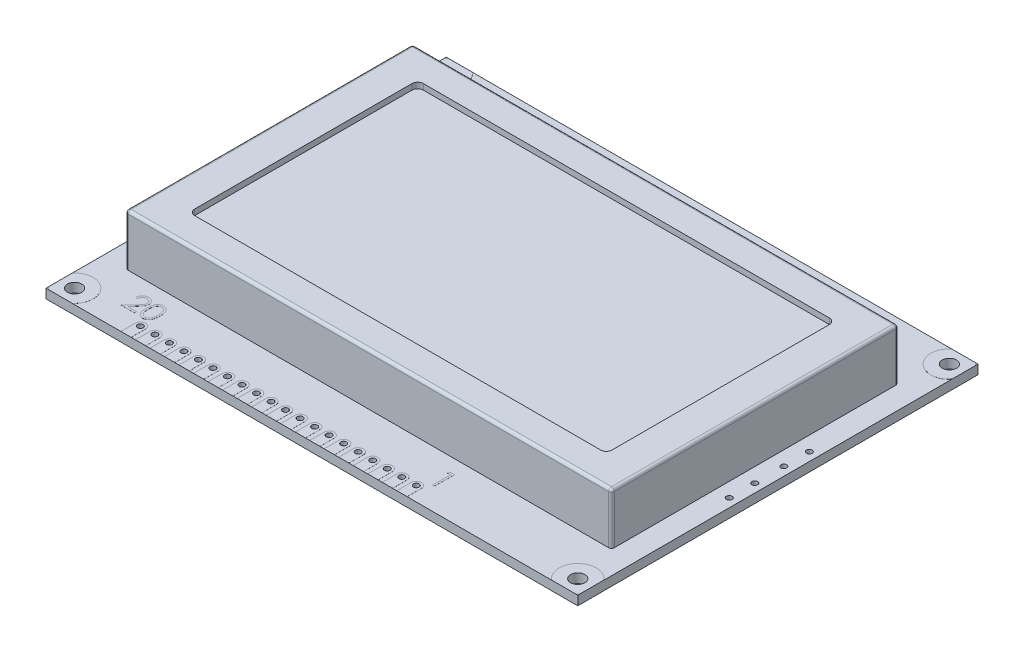
SolidWorks part; units mm, degrees
material "A-Glass Fiber"
ref_plane "Front Plane" through (0, 0, 0) normal (0, 0, 1) x (1, 0, 0)
ref_plane "Top Plane" through (0, 0, 0) normal (0, 1, 0) x (1, 0, 0)
ref_plane "Right Plane" through (0, 0, 0) normal (1, 0, 0) x (0, 0, -1)
sketch "Sketch1" plane through (0, 0, 0) normal (0, 1, 0) x (1, 0, 0)
  line L0 (2.5, 67.5) -> (90.5, 67.5) construction
  line L1 (0, 0) -> (93, 0)
  line L2 (0, 0) -> (0, 70)
  line L3 (0, 70) -> (93, 70)
  line L4 (93, 0) -> (93, 70)
  line L5 (2.5, 2.5) -> (90.5, 2.5) construction
  line L6 (90.5, 2.5) -> (90.5, 67.5) construction
  line L7 (2.5, 67.5) -> (2.5, 2.5) construction
  line L8 (90.5, 35) -> (91.5, 35) construction
  line L9 (91.5, 37.54) -> (91.5, 32.46) construction
  line L10 (91.5, 37.54) -> (91.5, 42) construction
  line L11 (91.5, 32.46) -> (91.5, 28) construction
  circle A0 centre (2.5, 67.5) radius 1.25
  circle A1 centre (90.5, 67.5) radius 1.25
  circle A2 centre (90.5, 2.5) radius 1.25
  circle A3 centre (2.5, 2.5) radius 1.25
  circle A4 centre (14, 2.5) radius 0.5
  circle A5 centre (16.54, 2.5) radius 0.5
  circle A6 centre (19.08, 2.5) radius 0.5
  circle A7 centre (21.62, 2.5) radius 0.5
  circle A8 centre (24.16, 2.5) radius 0.5
  circle A9 centre (26.7, 2.5) radius 0.5
  circle A10 centre (29.24, 2.5) radius 0.5
  circle A11 centre (31.78, 2.5) radius 0.5
  circle A12 centre (34.32, 2.5) radius 0.5
  circle A13 centre (36.86, 2.5) radius 0.5
  circle A14 centre (39.4, 2.5) radius 0.5
  circle A15 centre (41.94, 2.5) radius 0.5
  circle A16 centre (44.48, 2.5) radius 0.5
  circle A17 centre (47.02, 2.5) radius 0.5
  circle A18 centre (49.56, 2.5) radius 0.5
  circle A19 centre (52.1, 2.5) radius 0.5
  circle A20 centre (54.64, 2.5) radius 0.5
  circle A21 centre (57.18, 2.5) radius 0.5
  circle A22 centre (59.72, 2.5) radius 0.5
  circle A23 centre (62.26, 2.5) radius 0.5
  circle A24 centre (91.5, 42) radius 0.5
  circle A25 centre (91.5, 37.54) radius 0.5
  circle A26 centre (91.5, 32.46) radius 0.5
  circle A27 centre (91.5, 28) radius 0.5
  point P57 (91.5, 35)
  dimension "D3" = 2.5
  dimension "D9" = 1
  dimension "D13" = 1
  dimension "D1" = 93
  dimension "D2" = 70
  dimension "D4" = 2.5
  dimension "D5" = 2.5
  dimension "D6" = 2.5
  dimension "D7" = 2.5
  dimension "D8" = 14
  dimension "D11" = 5.08
  dimension "D12" = 14
  dimension "D14" = 1.5
  dimension "D10" = 20
extrude "Boss-Extrude1" add sketch "Sketch1" along normal blind 1.6
sketch "Sketch4" plane through (0, 0, 0) normal (0, 1, 0) x (1, 0, 0)
  line L0 (13.1, 2.5) -> (13.1, 0)
  line L1 (0, 0) -> (93, 0) construction
  line L2 (13.1, 0) -> (14.9, 0)
  line L3 (14.9, 0) -> (14.9, 2.5)
  line L4 (15.64, 2.5) -> (15.64, 0)
  line L5 (15.64, 0) -> (17.44, 0)
  line L6 (17.44, 0) -> (17.44, 2.5)
  line L7 (18.18, 2.5) -> (18.18, 0)
  line L8 (18.18, 0) -> (19.98, 0)
  line L9 (19.98, 0) -> (19.98, 2.5)
  line L10 (20.72, 2.5) -> (20.72, 0)
  line L11 (20.72, 0) -> (22.52, 0)
  line L12 (22.52, 0) -> (22.52, 2.5)
  line L13 (23.26, 2.5) -> (23.26, 0)
  line L14 (23.26, 0) -> (25.06, 0)
  line L15 (25.06, 0) -> (25.06, 2.5)
  line L16 (25.8, 2.5) -> (25.8, 0)
  line L17 (25.8, 0) -> (27.6, 0)
  line L18 (27.6, 0) -> (27.6, 2.5)
  line L19 (28.34, 2.5) -> (28.34, 0)
  line L20 (28.34, 0) -> (30.14, 0)
  line L21 (30.14, 0) -> (30.14, 2.5)
  line L22 (30.88, 2.5) -> (30.88, 0)
  line L23 (30.88, 0) -> (32.68, 0)
  line L24 (32.68, 0) -> (32.68, 2.5)
  line L25 (33.42, 2.5) -> (33.42, 0)
  line L26 (33.42, 0) -> (35.22, 0)
  line L27 (35.22, 0) -> (35.22, 2.5)
  line L28 (35.96, 2.5) -> (35.96, 0)
  line L29 (35.96, 0) -> (37.76, 0)
  line L30 (37.76, 0) -> (37.76, 2.5)
  line L31 (38.5, 2.5) -> (38.5, 0)
  line L32 (38.5, 0) -> (40.3, 0)
  line L33 (40.3, 0) -> (40.3, 2.5)
  line L34 (41.04, 2.5) -> (41.04, 0)
  line L35 (41.04, 0) -> (42.84, 0)
  line L36 (42.84, 0) -> (42.84, 2.5)
  line L37 (43.58, 2.5) -> (43.58, 0)
  line L38 (43.58, 0) -> (45.38, 0)
  line L39 (45.38, 0) -> (45.38, 2.5)
  line L40 (46.12, 2.5) -> (46.12, 0)
  line L41 (46.12, 0) -> (47.92, 0)
  line L42 (47.92, 0) -> (47.92, 2.5)
  line L43 (48.66, 2.5) -> (48.66, 0)
  line L44 (48.66, 0) -> (50.46, 0)
  line L45 (50.46, 0) -> (50.46, 2.5)
  line L46 (51.2, 2.5) -> (51.2, 0)
  line L47 (51.2, 0) -> (53, 0)
  line L48 (53, 0) -> (53, 2.5)
  line L49 (53.74, 2.5) -> (53.74, 0)
  line L50 (53.74, 0) -> (55.54, 0)
  line L51 (55.54, 0) -> (55.54, 2.5)
  line L52 (56.28, 2.5) -> (56.28, 0)
  line L53 (56.28, 0) -> (58.08, 0)
  line L54 (58.08, 0) -> (58.08, 2.5)
  line L55 (58.82, 2.5) -> (58.82, 0)
  line L56 (58.82, 0) -> (60.62, 0)
  line L57 (60.62, 0) -> (60.62, 2.5)
  line L58 (61.36, 2.5) -> (61.36, 0)
  line L59 (61.36, 0) -> (63.16, 0)
  line L60 (63.16, 0) -> (63.16, 2.5)
  line L61 (0, 4.5767) -> (0, 0.4233)
  line L62 (0, 70) -> (0, 0) construction
  line L63 (0.4233, 0) -> (4.5767, 0)
  line L64 (4.5767, 70) -> (0.4233, 70)
  line L65 (93, 70) -> (0, 70) construction
  line L66 (0, 69.5767) -> (0, 65.4233)
  line L67 (88.4233, 70) -> (92.5767, 70)
  line L68 (93, 69.5767) -> (93, 65.4233)
  line L69 (93, 0) -> (93, 70) construction
  line L70 (88.4233, 0) -> (92.5767, 0)
  line L71 (93, 4.5767) -> (93, 0.4233)
  arc A0 (13.1, 2.5) -> (14.9, 2.5) centre (14, 2.5) cw
  circle A1 centre (14, 2.5) radius 0.5
  arc A2 (15.64, 2.5) -> (17.44, 2.5) centre (16.54, 2.5) cw
  circle A3 centre (16.54, 2.5) radius 0.5
  arc A4 (18.18, 2.5) -> (19.98, 2.5) centre (19.08, 2.5) cw
  circle A5 centre (19.08, 2.5) radius 0.5
  arc A6 (20.72, 2.5) -> (22.52, 2.5) centre (21.62, 2.5) cw
  circle A7 centre (21.62, 2.5) radius 0.5
  arc A8 (23.26, 2.5) -> (25.06, 2.5) centre (24.16, 2.5) cw
  circle A9 centre (24.16, 2.5) radius 0.5
  arc A10 (25.8, 2.5) -> (27.6, 2.5) centre (26.7, 2.5) cw
  circle A11 centre (26.7, 2.5) radius 0.5
  arc A12 (28.34, 2.5) -> (30.14, 2.5) centre (29.24, 2.5) cw
  circle A13 centre (29.24, 2.5) radius 0.5
  arc A14 (30.88, 2.5) -> (32.68, 2.5) centre (31.78, 2.5) cw
  circle A15 centre (31.78, 2.5) radius 0.5
  arc A16 (33.42, 2.5) -> (35.22, 2.5) centre (34.32, 2.5) cw
  circle A17 centre (34.32, 2.5) radius 0.5
  arc A18 (35.96, 2.5) -> (37.76, 2.5) centre (36.86, 2.5) cw
  circle A19 centre (36.86, 2.5) radius 0.5
  arc A20 (38.5, 2.5) -> (40.3, 2.5) centre (39.4, 2.5) cw
  circle A21 centre (39.4, 2.5) radius 0.5
  arc A22 (41.04, 2.5) -> (42.84, 2.5) centre (41.94, 2.5) cw
  circle A23 centre (41.94, 2.5) radius 0.5
  arc A24 (43.58, 2.5) -> (45.38, 2.5) centre (44.48, 2.5) cw
  circle A25 centre (44.48, 2.5) radius 0.5
  arc A26 (46.12, 2.5) -> (47.92, 2.5) centre (47.02, 2.5) cw
  circle A27 centre (47.02, 2.5) radius 0.5
  arc A28 (48.66, 2.5) -> (50.46, 2.5) centre (49.56, 2.5) cw
  circle A29 centre (49.56, 2.5) radius 0.5
  arc A30 (51.2, 2.5) -> (53, 2.5) centre (52.1, 2.5) cw
  circle A31 centre (52.1, 2.5) radius 0.5
  arc A32 (53.74, 2.5) -> (55.54, 2.5) centre (54.64, 2.5) cw
  circle A33 centre (54.64, 2.5) radius 0.5
  arc A34 (56.28, 2.5) -> (58.08, 2.5) centre (57.18, 2.5) cw
  circle A35 centre (57.18, 2.5) radius 0.5
  arc A36 (58.82, 2.5) -> (60.62, 2.5) centre (59.72, 2.5) cw
  circle A37 centre (59.72, 2.5) radius 0.5
  arc A38 (61.36, 2.5) -> (63.16, 2.5) centre (62.26, 2.5) cw
  circle A39 centre (62.26, 2.5) radius 0.5
  arc A40 (0, 0.4233) -> (0.4233, 0) centre (2.5, 2.5) ccw
  circle A41 centre (2.5, 2.5) radius 1.25
  circle A42 centre (90.5, 67.5) radius 1.25
  arc A43 (88.4233, 70) -> (93, 65.4233) centre (90.5, 67.5) ccw
  circle A44 centre (2.5, 67.5) radius 1.25
  arc A45 (0.4233, 70) -> (0, 69.5767) centre (2.5, 67.5) ccw
  circle A46 centre (90.5, 2.5) radius 1.25
  arc A47 (93, 4.5767) -> (88.4233, 0) centre (90.5, 2.5) ccw
  arc A48 (4.5767, 0) -> (0, 4.5767) centre (2.5, 2.5) ccw
  arc A49 (0, 65.4233) -> (4.5767, 70) centre (2.5, 67.5) ccw
  arc A50 (93, 69.5767) -> (92.5767, 70) centre (90.5, 67.5) ccw
  arc A51 (92.5767, 0) -> (93, 0.4233) centre (90.5, 2.5) ccw
  dimension "D1" = 20
  dimension "D2" = 0.9
  dimension "D3" = 6.5
extrude "Boss-Extrude2" add sketch "Sketch4" along normal blind 1.61 and the other way blind 0.01
sketch "Sketch5" plane through (0, 0, 0) normal (0, 1, 0) x (1, 0, 0)
  line L0 (0, 70) -> (93, 0) construction
  line L2 (4, 60.1) -> (89, 60.1)
  line L3 (4, 60.1) -> (4, 9.9)
  line L4 (4, 9.9) -> (89, 9.9)
  line L5 (89, 60.1) -> (89, 9.9)
  line L6 (4, 60.1) -> (89, 9.9) construction
  line L7 (4, 9.9) -> (89, 60.1) construction
  point P4 (46.5, 35)
  dimension "D1" = 50.2
  dimension "D2" = 85
extrude "Boss-Extrude3" add sketch "Sketch5" along normal blind 9 from surface starting at face at (91.5, 1.6, -27.5)
fillet "Fillet1" radius 0.5 8 edges at (89, 6.1, -9.9) (89, 6.1, -60.1) (89, 10.6, -35) (46.5, 10.6, -60.1) (4, 6.1, -60.1) (46.5, 10.6, -9.9) (4, 10.6, -35) (4, 6.1, -9.9)
sketch "Sketch6" plane through (0, 0, 0) normal (0, 1, 0) x (1, 0, 0)
  line L0 (0, 70) -> (93, 0) construction
  line L2 (11, 55) -> (82, 55)
  line L3 (10, 54) -> (10, 16)
  line L4 (11, 15) -> (82, 15)
  line L5 (83, 54) -> (83, 16)
  line L6 (10, 55) -> (83, 15) construction
  line L7 (10, 15) -> (83, 55) construction
  arc A0 (82, 55) -> (83, 54) centre (82, 54) cw
  arc A1 (82, 15) -> (83, 16) centre (82, 16) ccw
  arc A2 (10, 16) -> (11, 15) centre (11, 16) ccw
  arc A3 (11, 55) -> (10, 54) centre (11, 54) ccw
  point P4 (46.5, 35)
  dimension "D3" = 1
  dimension "D1" = 73
  dimension "D2" = 40
extrude "Cut-Extrude1" cut sketch "Sketch6" against normal blind 1 from surface starting at face at (46.5, 10.6, -35)
sketch "Sketch7" plane through (0, 0, 0) normal (0, 1, 0) x (1, 0, 0)
  text T0 "1"
  text T1 "20"
extrude "Boss-Extrude4" add sketch "Sketch7" along normal blind 0.01 from surface starting at face at (38.8909, 1.6, -4.5227)
sketch "Sketch8" plane through (0, 0, 0) normal (0, 1, 0) x (1, 0, 0)
  circle A0 centre (19.3751, 34.1638) radius 7.5
  circle A1 centre (38.6082, 39.2856) radius 7.5
  circle A2 centre (59.3046, 35.4181) radius 7.5
  dimension "D1" = 15
extrude "Boss-Extrude5" add sketch "Sketch8" against normal blind 3
fillet "Fillet2" radius 9 3 edges at (59.3046, -3, -27.9181) (38.6082, -3, -31.7856) (19.3751, -3, -26.6638)
